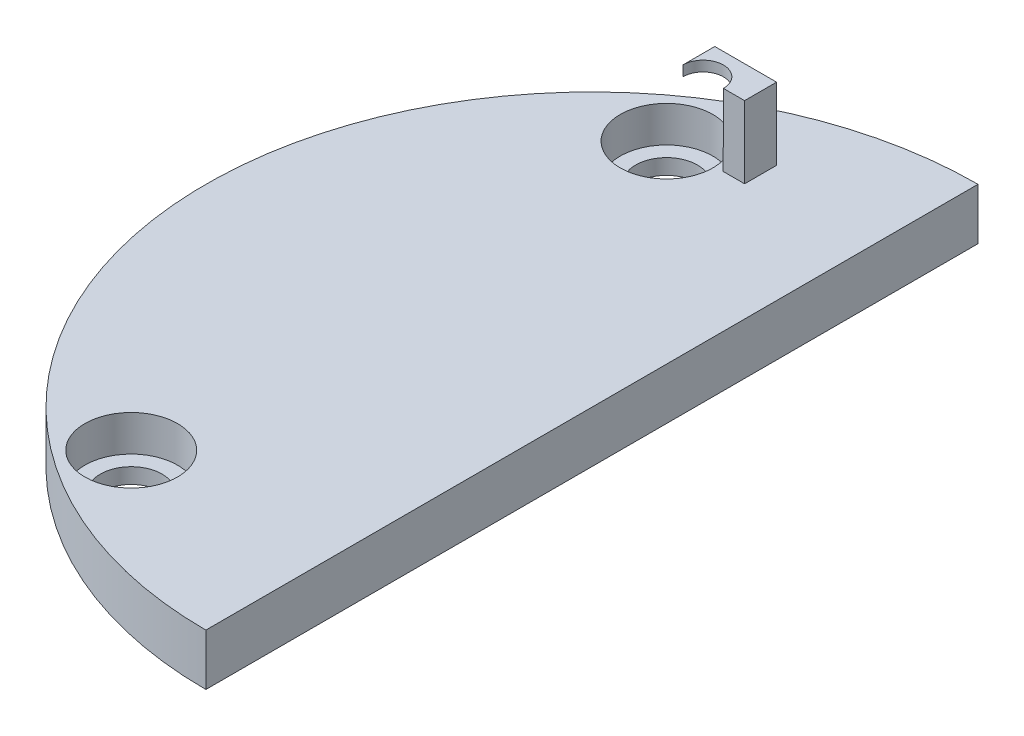
SolidWorks part; units mm, degrees
ref_plane "Ebene vorne" through (0, 0, 0) normal (0, 0, 1) x (1, 0, 0)
ref_plane "Ebene oben" through (0, 0, 0) normal (0, 1, 0) x (1, 0, 0)
ref_plane "Ebene rechts" through (0, 0, 0) normal (1, 0, 0) x (0, 0, -1)
sketch "Skizze1" plane through (0, 0, 0) normal (0, 1, 0) x (1, 0, 0)
  line L0 (0, 0) -> (0, -75)
  line L1 (0, -37.5) -> (-48.465, -37.5) construction
  arc A1 (0, -75) -> (0, 0) centre (0, -37.5) cw
  dimension "D1" = 75
extrude "Aufsatz-Linear austragen1" add sketch "Skizze1" along normal blind 5
sketch "Skizze11" plane through (0, 5, 0) normal (0, 1, 0) x (1, 0, 0)
  line L0 (0, -37.5) -> (-37.5, -37.5) construction
  line L1 (0, -75) -> (0, 0) construction
  line L2 (-18.75, -37.5) -> (-18.75, -1.2821) construction
  line L3 (-18.75, -1.2821) -> (-18.75, -74.2151) construction
  arc A0 (0, 0) -> (0, -75) centre (0, -37.5) ccw construction
  circle A1 centre (-18.75, -11.5) radius 4.5
  circle A2 centre (-18.75, -63.5) radius 4.5
  dimension "D1" = 52
extrude "Schnitt-Linear austragen1" cut sketch "Skizze11" against normal blind 3.5
sketch "Skizze12" plane through (0, 1.5, 0) normal (0, 1, 0) x (1, 0, 0)
  circle A0 centre (-18.75, -63.5) radius 3
  circle A1 centre (-18.75, -11.5) radius 3
extrude "Schnitt-Linear austragen2" cut sketch "Skizze12" against normal blind 1.5
sketch "Skizze13" plane through (0, 5, 0) normal (0, 1, 0) x (1, 0, 0)
  line L0 (-13.4591, -11.2984) -> (-11.3733, -11.2984)
  line L1 (-11.3733, -8.1916) -> (-13.4591, -8.1916)
  line L2 (-13.4591, -8.1916) -> (-13.4591, -11.2984)
  line L3 (-11.3733, -8.1916) -> (-11.3733, -11.2984)
extrude "Aufsatz-Linear austragen2" add sketch "Skizze13" along normal blind 6
sketch "Skizze14" plane through (0, 11, 0) normal (0, 1, 0) x (1, 0, 0)
  line L0 (-11.3733, -8.1916) -> (-11.3733, -11.2984)
  line L1 (-11.3733, -11.2984) -> (-17.3733, -11.2984)
  line L2 (-17.3733, -11.2984) -> (-17.3733, -8.1916)
  line L3 (-17.3733, -8.1916) -> (-11.3733, -8.1916)
extrude "Aufsatz-Linear austragen3" add sketch "Skizze14" along normal blind 1
sketch "Skizze16" plane through (0, 12, 0) normal (0, 1, 0) x (1, 0, 0)
  line L0 (-17.3733, -11.2984) -> (-13.43, -11.2984)
  line L1 (-17.3733, -11.2984) -> (-11.3733, -11.2984) construction
  arc A0 (-13.43, -11.2984) -> (-17.3733, -11.2984) centre (-15.4017, -11.2984) ccw
extrude "Schnitt-Linear austragen3" cut sketch "Skizze16" against normal blind 5
